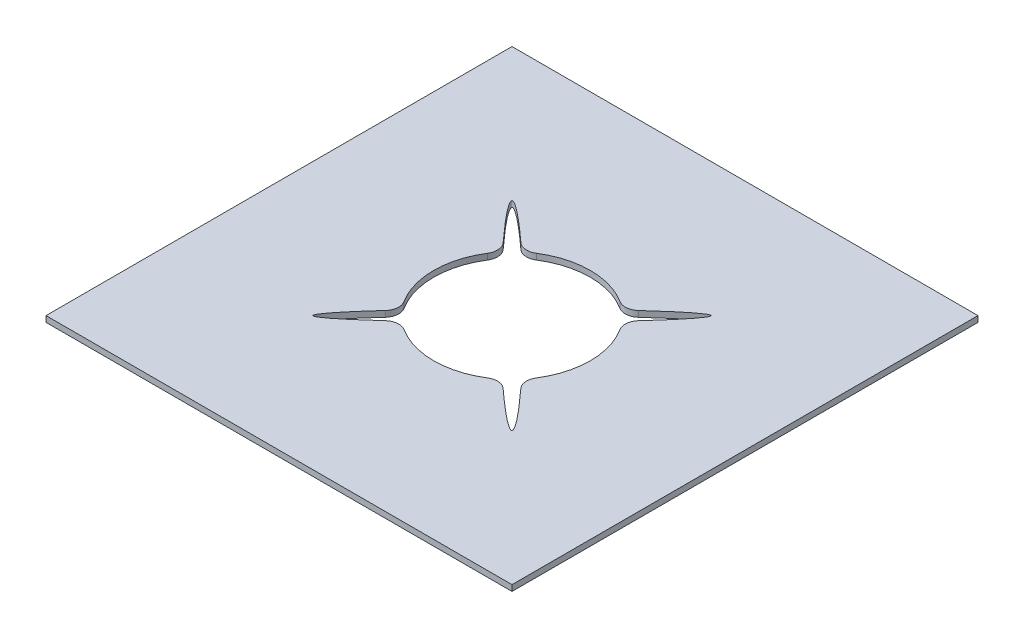
SolidWorks part; units mm, degrees
ref_plane "Front Plane" through (0, 0, 0) normal (0, 0, 1) x (1, 0, 0)
ref_plane "Top Plane" through (0, 0, 0) normal (0, 1, 0) x (1, 0, 0)
ref_plane "Right Plane" through (0, 0, 0) normal (1, 0, 0) x (0, 0, -1)
sketch "Sketch1" plane through (0, 0, 0) normal (0, 1, 0) x (1, 0, 0)
  line L1 (-229.8387, 211.6935) -> (270.1613, 211.6935)
  line L2 (-229.8387, 211.6935) -> (-229.8387, -288.3065)
  line L3 (-229.8387, -288.3065) -> (270.1613, -288.3065)
  line L4 (270.1613, 211.6935) -> (270.1613, -288.3065)
  dimension "D1" = 500
  dimension "D2" = 500
extrude "Boss-Extrude1" add sketch "Sketch1" along normal blind 6.35
sketch "Sketch2" plane through (0, 6.35, 0) normal (0, 1, 0) x (1, 0, 0)
  line L0 (270.1613, -288.3065) -> (270.1613, 211.6935) construction
  line L1 (-229.8387, -288.3065) -> (270.1613, -288.3065) construction
  circle A0 centre (20.1613, -38.3065) radius 84
  point P4 (270.1613, -38.3065)
  point P7 (20.1613, -288.3065)
  dimension "D1" = 168
  dimension "D2" = 0
  dimension "D3" = 0
extrude "Cut-Extrude1" cut sketch "Sketch2" against normal blind 6.35
sketch "Sketch3" plane through (0, 6.35, 0) normal (0, 1, 0) x (1, 0, 0)
  line L0 (20.1613, -38.3065) -> (-145.9674, 127.9051)
  line L1 (-38.1612, 9.4359) -> (-27.5558, 20.0437)
  line L2 (-27.581, -96.6289) -> (-38.1889, -86.0236)
  line L3 (78.4837, -86.0488) -> (67.8784, -96.6566)
  line L4 (67.9036, 20.016) -> (78.5115, 9.4107)
  circle A0 centre (20.1613, -38.3065) radius 84 construction
  conic Q0 (-38.1612, 9.4359) -> (-27.5558, 20.0437) control (-209.6787, 191.473) rho 0.304
  conic Q1 (-27.581, -96.6289) -> (-38.1889, -86.0236) control (-209.6181, -268.1464) rho 0.304
  conic Q2 (78.4837, -86.0488) -> (67.8784, -96.6566) control (250.0013, -268.0859) rho 0.304
  conic Q3 (67.9036, 20.016) -> (78.5115, 9.4107) control (249.9407, 191.5335) rho 0.304
  point P5 (-32.8585, 14.7398)
  point P23 (20.1663, -38.306)
  point P25 (20.1613, -38.3065)
  dimension "D1" = 235
  dimension "D2" = 75
  dimension "D3" = 0
  dimension "D4" = 15
  dimension "D6" = 76
  dimension "D7" = 0
  dimension "D8" = 250
  dimension "D5" = 4
extrude "Cut-Extrude2" cut sketch "Sketch3" against normal blind 6.35 contours Q1 L2 | Q0 L1 | L3 Q2 | L4 Q3
fillet "Fillet1" radius 15 8 edges at (-44.1285, 3.175, 92.3696) (-33.9274, 3.175, 102.5747) (74.2244, 3.175, 102.5962) (84.4296, 3.175, 92.3952) (-44.107, 3.175, -15.7823) (-33.9019, 3.175, -25.9833) (74.25, 3.175, -25.9618) (84.4511, 3.175, -15.7567)
